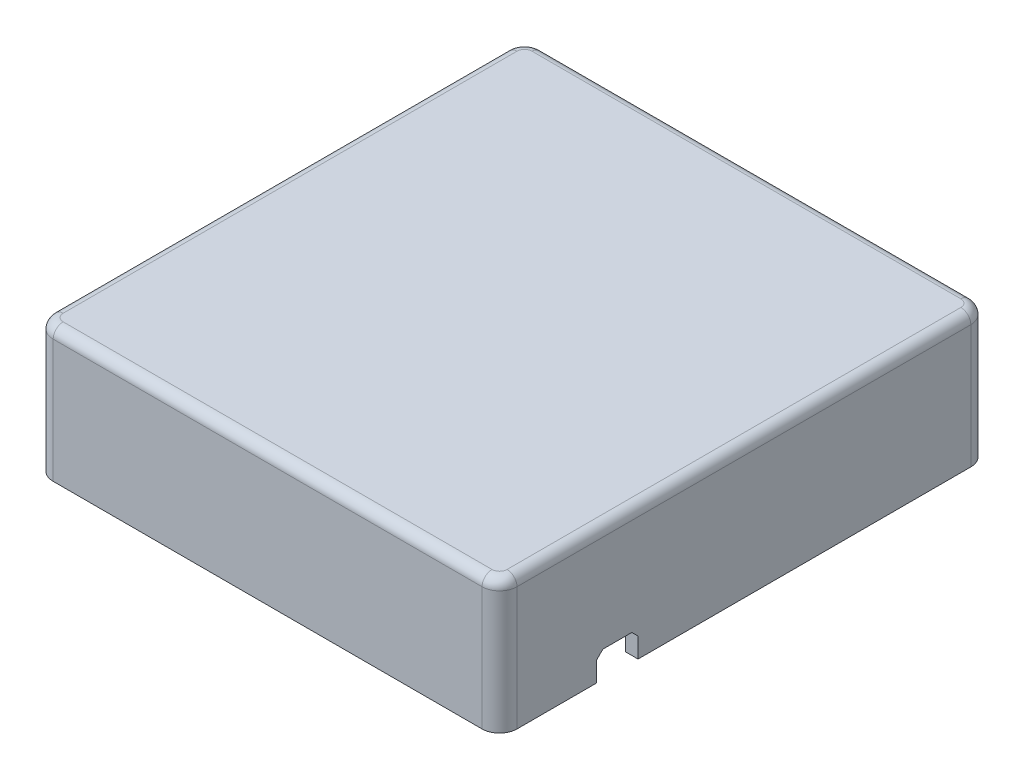
SolidWorks part; units mm, degrees
ref_plane "Front Plane" through (0, 0, 0) normal (0, 0, 1) x (1, 0, 0)
ref_plane "Top Plane" through (0, 0, 0) normal (0, 1, 0) x (1, 0, 0)
ref_plane "Right Plane" through (0, 0, 0) normal (1, 0, 0) x (0, 0, -1)
sketch "Sketch1" plane through (0, 0, 0) normal (0, 1, 0) x (1, 0, 0)
  line L0 (157.4, 196) -> (157.4, 191)
  line L1 (0, 0) -> (186, 0)
  line L2 (0, 0) -> (0, 196)
  line L3 (0, 196) -> (186, 196)
  line L4 (186, 0) -> (186, 196)
  line L5 (157.4, 191) -> (82.4, 191)
  line L6 (82.4, 191) -> (82.4, 196)
  line L7 (158.2, 196) -> (158.2, 191)
  line L8 (81.6, 191) -> (81.6, 196)
  line L9 (81.6, 191) -> (82.4, 191)
  line L10 (158.2, 191) -> (157.4, 191)
  line L11 (181, 39.75) -> (186, 39.75)
  line L12 (186, 54.75) -> (181, 54.75)
  line L13 (5, 191) -> (181, 191)
  line L14 (181, 5) -> (181, 191)
  line L15 (5, 5) -> (181, 5)
  line L16 (5, 5) -> (5, 191)
  line L17 (186, 55.55) -> (181, 55.55)
  line L18 (181, 38.95) -> (186, 38.95)
  dimension "D1" = 186
  dimension "D2" = 196
  dimension "D3" = 28.6
  dimension "D4" = 75
  dimension "D8" = 39.75
  dimension "D9" = 15
  dimension "D5" = 0.8
  dimension "D6" = 0.8
  dimension "D7" = 5
  dimension "D10" = 0.8
extrude "Boss-Extrude1" add sketch "Sketch1" against normal blind 3 contours L3 L4 L1 L2
extrude "Boss-Extrude2" add sketch "Sketch1<3>" against normal blind 50.4 from surface contours L15 L16 L13 L8 L3 L2 L1 L4 L7 L14 | L17 L4 L3 L7 L13 L14 region at (181.5587, 0, -135.2337) region at (78.8979, 0, -193.5) starting at face at (93, -3, -98)
sketch "Sketch1<3>" plane through (0, 0, 0) normal (0, 1, 0) x (1, 0, 0) same geometry as "Sketch1"
chamfer "Chamfer1" distance 10 angle 45 4 edges at (5, -28.2, -5) (181, -28.2, -5) (181, -28.2, -191) (5, -28.2, -191)
extrude "Boss-Extrude3" add sketch "Sketch1<4>" against normal offset from surface (42.9 mm away) 10.5 contours L4 L17 L14 L12 | L14 L11 L4 L12 | L14 L18 L4 L11 region at (183.5, 0, -55.15) region at (183.5, 0, -47.25) region at (183.5, 0, -39.35) up to face at (174.4857, -53.4, -152.3)
sketch "Sketch1<4>" plane through (0, 0, 0) normal (0, 1, 0) x (1, 0, 0) same geometry as "Sketch1"
chamfer "Chamfer2" distance 2.5 angle 45 2 edges at (183.5, -42.9, -38.95) (183.5, -42.9, -55.55)
sketch "Sketch2" plane through (0, -53.4, 0) normal (0, -1, 0) x (1, 0, 0)
  line L0 (10, -10) -> (6.5, -6.5) construction
  line L1 (5, -15) -> (15, -5) construction
  line L2 (171, -5) -> (15, -5) construction
  line L3 (0, -98) -> (186, -98) construction
  line L4 (0, -196) -> (0, 0) construction
  line L5 (186, -196) -> (186, -55.55) construction
  line L6 (93, 0) -> (93, -196) construction
  line L7 (186, 0) -> (0, 0) construction
  line L8 (81.6, -196) -> (158.2, -196) construction
  circle A0 centre (6.5, -6.5) radius 2.35
  circle A1 centre (6.5, -6.5) radius 1.8
  circle A2 centre (179.5, -6.5) radius 2.35
  circle A3 centre (179.5, -6.5) radius 1.8
  circle A4 centre (179.5, -189.5) radius 2.35
  circle A5 centre (179.5, -189.5) radius 1.8
  circle A6 centre (6.5, -189.5) radius 2.35
  circle A7 centre (6.5, -189.5) radius 1.8
  dimension "D1" = 4.7
  dimension "D2" = 3.6
  dimension "D3" = 45
  dimension "D4" = 8.5
extrude "Cut-Extrude2" cut sketch "Sketch2" against normal blind 4.5
extrude "Cut-Extrude3" cut sketch "Sketch2<3>" against normal blind 8 contours A1 | A7 | A5 | A3 region at (6.5, -53.4, -6.5) region at (179.5, -53.4, -189.5) region at (6.5, -53.4, -189.5)
sketch "Sketch2<3>" plane through (0, -53.4, 0) normal (0, -1, 0) x (1, 0, 0) same geometry as "Sketch2"
fillet "Fillet1" radius 7 4 edges at (186, -26.7, -196) (186, -26.7, 0) (0, -26.7, 0) (0, -26.7, -196)
fillet "Fillet2" radius 4 8 edges at (183.9497, 0, -2.0503) (93, 0, 0) (2.0503, 0, -2.0503) (0, 0, -98) (2.0503, 0, -193.9497) (93, 0, -196) (183.9497, 0, -193.9497) (186, 0, -98)
